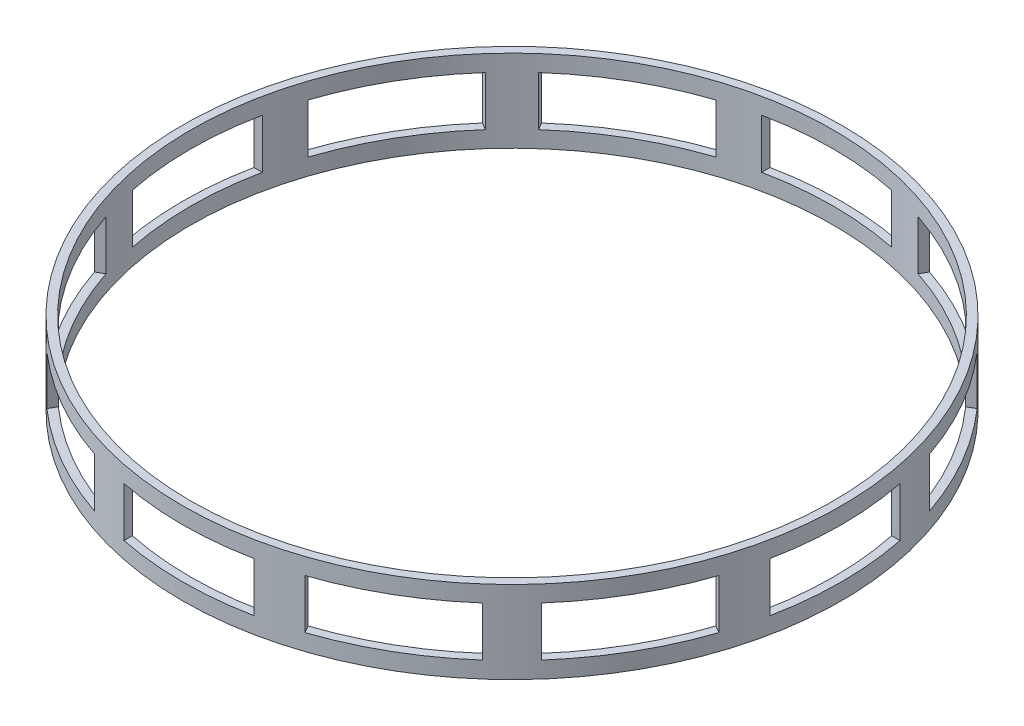
SolidWorks part; units mm, degrees
ref_plane "Front Plane" through (0, 0, 0) normal (0, 0, 1) x (1, 0, 0)
ref_plane "Top Plane" through (0, 0, 0) normal (0, 1, 0) x (1, 0, 0)
ref_plane "Right Plane" through (0, 0, 0) normal (1, 0, 0) x (0, 0, -1)
sketch "Sketch1" plane through (0, 0, 0) normal (0, 1, 0) x (1, 0, 0)
  circle A0 centre (0, 0) radius 100
  circle A1 centre (0, 0) radius 97.5
  dimension "D1" = 200
  dimension "D2" = 195
extrude "Boss-Extrude1" add sketch "Sketch1" along normal blind 25
sketch "Sketch2" plane through (0, 0, 0) normal (0, 0, 1) x (1, 0, 0)
  line L1 (-5.291, 20) -> (19.709, 20)
  line L2 (-5.291, 20) -> (-5.291, 5)
  line L3 (-5.291, 5) -> (19.709, 5)
  line L4 (19.709, 20) -> (19.709, 5)
  dimension "D1" = 5
  dimension "D2" = 15
  dimension "D3" = 25
extrude "Cut-Extrude1" cut sketch "Sketch2" against normal through all both and the other way through all
pattern_circular "CirPattern1" count 12 over 360 about axis through (0, 25, 0) along (0, -1, 0) of "Cut-Extrude1" reverse direction yes
